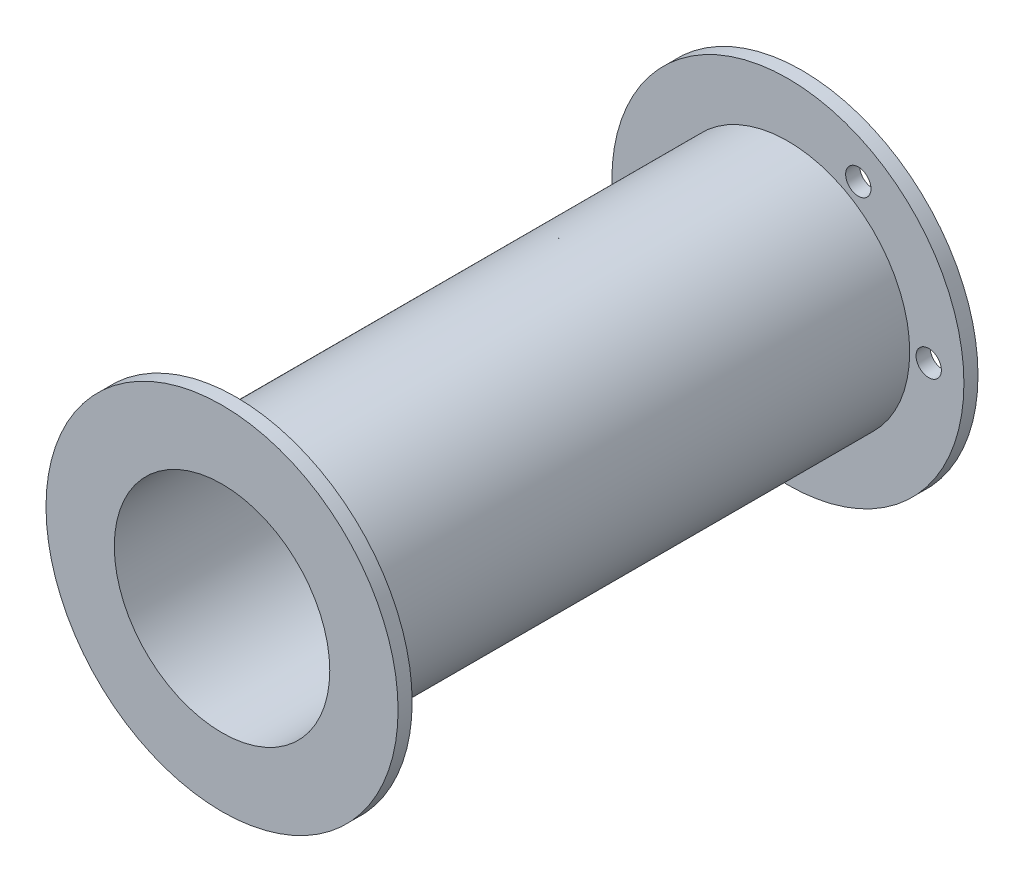
SolidWorks part; units mm, degrees
material "1060 Alloy"
ref_plane "Front Plane" through (0, 0, 0) normal (0, 0, 1) x (1, 0, 0)
ref_plane "Top Plane" through (0, 0, 0) normal (0, 1, 0) x (1, 0, 0)
ref_plane "Right Plane" through (0, 0, 0) normal (1, 0, 0) x (0, 0, -1)
sketch "Sketch1" plane through (0, 0, 0) normal (0, 0, 1) x (1, 0, 0)
  circle A0 centre (0, 0) radius 7.65
  circle A1 centre (0, 0) radius 8.65
  dimension "D1" = 15.3
  dimension "D2" = 17.3
extrude "Boss-Extrude1" add sketch "Sketch1" along normal blind 40.18
sketch "Sketch2" plane through (0, 0, 0) normal (0, 0, -1) x (-1, 0, 0)
  circle A0 centre (0, 0) radius 12.5
  circle A2 centre (0, 0) radius 7.65
  dimension "D1" = 25
extrude "Boss-Extrude2" add sketch "Sketch2" along normal blind 1
hole_wizard "M1.6 Clearance Hole1" positions "Sketch10" profile "Sketch11" hole size "M1.6" standard "ISO"
sketch "Sketch10" plane through (0, 0, 0) normal (0, 0, 1) x (1, 0, 0)
  point P0 (-10, 0)
  dimension "D1" = 10
sketch "Sketch11" plane through (-10, 0, 0) normal (1, 0, 0) x (0, -1, 0)
  line L0 (0, 0) -> (0, 5.5408)
  line L1 (0, 5.5408) -> (0.9, 5)
  line L2 (0.9, 5) -> (0.9, 0)
  line L5 (0.9, 0) -> (0, 0)
  line L10 (0, 5.5408) -> (-0.9, 5) construction
  line L11 (0, -6.35) -> (0, 107.95) construction
  dimension "Hole Dia." = 1.8
  dimension "Hole Depth" = 5
  dimension "Drill Angle" = 118
pattern_circular "CirPattern1" count 6 over 360 about axis through (0, 0, 0) along (0, 0, -1) skipping 1, 4 of "M1.6 Clearance Hole1"
ref_plane "Plane1" through (0, 0, 19.59) normal (0, 0, 1) x (1, 0, 0)
mirror "Mirror1" about plane through (0, 0, 19.59) normal (0, 0, 1) of "Boss-Extrude2"
